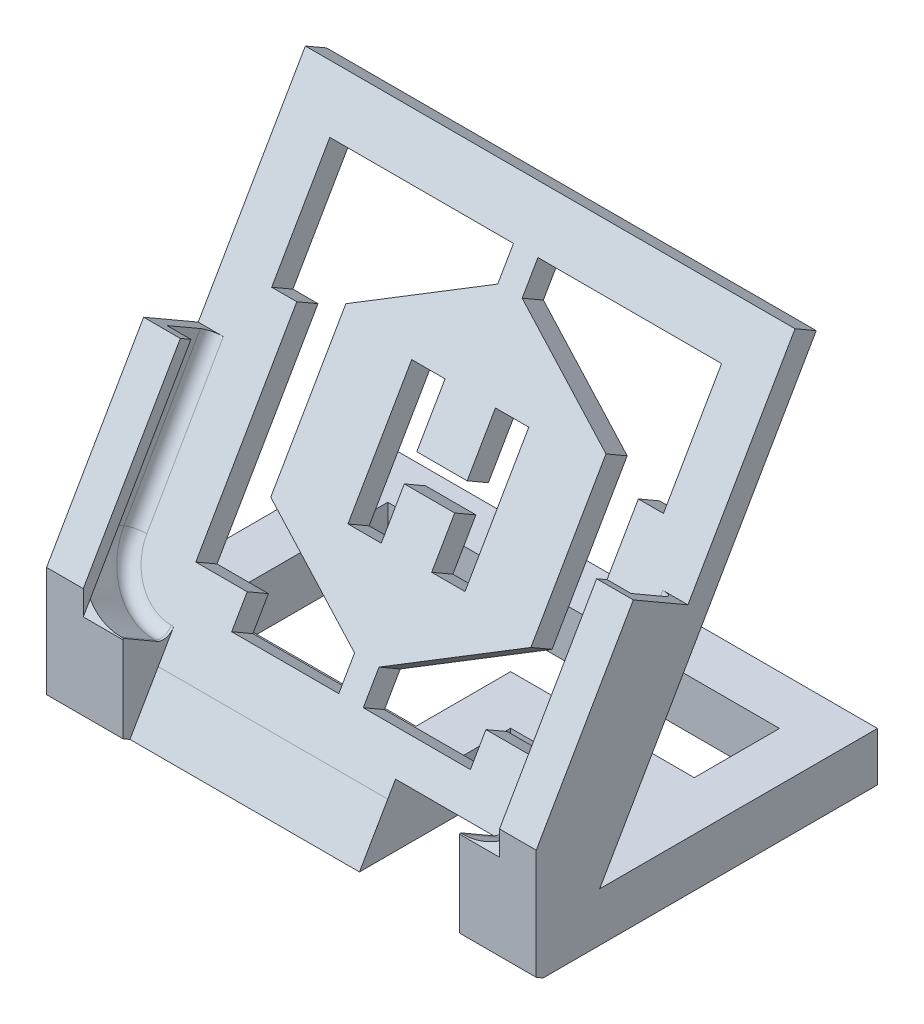
SolidWorks part; units mm, degrees
ref_plane "Front" through (0, 0, 0) normal (0, 0, 1) x (1, 0, 0)
ref_plane "Top" through (0, 0, 0) normal (0, 1, 0) x (1, 0, 0)
ref_plane "Right" through (0, 0, 0) normal (1, 0, 0) x (0, 0, -1)
sketch "Sketch1" plane through (0, 0, 0) normal (0, 1, 0) x (1, 0, 0)
  line L1 (-40, -25) -> (40, -25)
  line L2 (-40, -25) -> (-40, 25)
  line L3 (-40, 25) -> (40, 25)
  line L4 (40, -25) -> (40, 25)
  line L5 (-40, -25) -> (40, 25) construction
  line L6 (-40, 25) -> (40, -25) construction
  point P0 (0, 0)
  dimension "D1" = 80
  dimension "D2" = 50
extrude "Boss-Extrude1" add sketch "Sketch1" along normal blind 8
sketch "Sketch2" plane through (40, 0, 0) normal (1, 0, 0) x (0, 0, -1)
  line L0 (11.5359, 71.282) -> (-28.4641, 2)
  line L1 (11.5359, 71.282) -> (15, 69.282)
  line L2 (-28.4641, 2) -> (-25, 0)
  line L3 (15, 69.282) -> (-25, 0)
  line L4 (11.5359, 71.282) -> (-25, 0) construction
  line L5 (-28.4641, 2) -> (15, 69.282) construction
  line L6 (-25, 8) -> (-28.4641, 2)
  line L7 (-25, 0) -> (25, 0) construction
  line L8 (-25, 8) -> (25, 8) construction
  point P1 (-6.7321, 35.641)
  line M7 (25, 8) -> (-25, 8)
  dimension "D1" = 60
  dimension "D2" = 80
  dimension "D3" = 4
extrude "Boss-Extrude2" add sketch "Sketch2" against normal up to surface (80 mm away) contours L3 L1 L0 M7 up to face at (-40, 4, 0)
sketch "Sketch3" plane through (0, 12.8253, 22.2141) normal (0, 0.5, 0.866) x (1, 0, 0)
  line L0 (40, -2.5) -> (-40, -2.5)
  line L1 (40, 67.5) -> (40, -5.5718) construction
  line L2 (-40, -5.5718) -> (-40, 67.5) construction
  line L4 (-27.5, -2.5) -> (-27.5, -5.5718)
  line L5 (-40, -5.5718) -> (40, -5.5718) construction
  line L6 (0, -2.5) -> (0, -5.5718) construction
  line L7 (0, -5.5718) -> (-1.2175, -29.0774) construction
  line L8 (-37.9, -2.5) -> (-37.9, 32.5)
  line L9 (37.9, 32.5) -> (40, 32.5)
  line L10 (-37.9, 32.5) -> (-40, 32.5)
  line L11 (37.9, -2.5) -> (37.9, 32.5)
  line L12 (27.5, -2.5) -> (27.5, -5.5718)
  line L13 (-40, -12.5) -> (40, -12.5) construction
  line L14 (-40, -12.5) -> (40, -12.5)
  line M6 (-40, 67.5) -> (-40, -5.5718)
  line M7 (-40, -5.5718) -> (40, -5.5718)
  line M8 (40, -5.5718) -> (40, 67.5)
  dimension "D1" = 10
  dimension "D2" = 12.5
  dimension "D3" = 2.1
  dimension "D4" = 35
extrude "Boss-Extrude3" add sketch "Sketch3" along normal blind 8.3 contours L8 L10 L0 M6 | L4 L0 M6 M7 | L0 L12 M7 M8 | L11 L0 L9 M8
fillet "Fillet1" radius 10 2 edges at (-37.9, 12.7353, 27.0581) (37.9, 12.7353, 27.0581)
fillet "Fillet2" radius 2 6 edges at (27.7, 10.6603, 23.4641) (34.9711, 13.1968, 21.9996) (-27.7, 10.6603, 23.4641) (-34.9711, 13.1968, 21.9996) (37.9, 30.1458, 12.2141) (-37.9, 30.1458, 12.2141)
sketch "Sketch4" plane through (0, 0, 25) normal (0, 0, 1) x (1, 0, 0)
  line L4 (-40, 0) -> (40, 0)
  line L5 (40, 0) -> (40, 8)
  line L6 (27.5, 8) -> (-27.5, 8)
  line L7 (40, 0) -> (40, 8)
  line L8 (-40, 0) -> (40, 0)
  line L10 (27.5, 8) -> (-27.5, 8)
  line L14 (40, 8) -> (27.5, 8)
  line L15 (40, 8) -> (27.5, 8)
  line L16 (-27.5, 8) -> (-40, 8)
  line L17 (-27.5, 8) -> (-40, 8)
  line L18 (-40, 8) -> (-40, 0)
  line L19 (-40, 8) -> (-40, 0)
  dimension "D1" = 0
extrude "Boss-Extrude4" add sketch "Sketch4" along normal blind 10
chamfer "Chamfer2" distance 10 angle 60 1 edges at (0, 8, 35)
sketch "Sketch5" plane through (0, 12.8253, 22.2141) normal (0, 0.5, 0.866) x (1, 0, 0)
  line L0 (-27.5, -0.5) -> (-27.5, -5.5718) construction
  line L1 (-27.5, -0.5) -> (-27.5, -14.8094)
  line L2 (27.5, -0.5) -> (27.5, -5.5718) construction
  line L3 (27.5, -0.5) -> (27.5, -14.8094)
  line L6 (27.5, -5.5718) -> (-27.5, -5.5718)
  line L7 (-27.5, -5.5718) -> (-40, -5.5718)
  line L8 (-40, -5.5718) -> (-40, -14.8094)
  line L9 (-40, -14.8094) -> (40, -14.8094)
  line L10 (40, -14.8094) -> (40, -5.5718)
  line L11 (40, -5.5718) -> (27.5, -5.5718)
  line L12 (27.5, -5.5718) -> (-27.5, -5.5718)
  line L13 (-27.5, -5.5718) -> (-40, -5.5718)
  line L14 (-40, -5.5718) -> (-40, -14.8094)
  line L15 (-40, -14.8094) -> (40, -14.8094)
  line L16 (40, -14.8094) -> (40, -5.5718)
  line L17 (40, -5.5718) -> (27.5, -5.5718)
  line M8 (-27.5, -5.5718) -> (-40, -5.5718)
  line M9 (-40, -5.5718) -> (-40, -14.8094)
  line M10 (-40, -14.8094) -> (40, -14.8094)
  line M11 (40, -14.8094) -> (40, -5.5718)
  line M12 (40, -5.5718) -> (27.5, -5.5718)
  dimension "D1" = 0
extrude "Boss-Extrude5" add sketch "Sketch5" along normal up to surface (8.3 mm away) contours L1 M8 M9 M10 | L3 M12 M10 M11 up to face at (-34.3959, 23.6914, 25.5246)
sketch "Sketch6" plane through (0, 16.9753, 29.4021) normal (0, 0.5, 0.866) x (1, 0, 0)
  line L1 (-40, -14.8094) -> (-34, -14.8094)
  line L2 (-40, -14.8094) -> (-40, 32.5)
  line L3 (-40, 32.5) -> (-34, 32.5)
  line L4 (-34, -14.8094) -> (-34, 32.5)
  line L5 (40, -14.8094) -> (34, -14.8094)
  line L6 (-27.5, -2.5) -> (-27.9, -2.5)
  line L7 (-37.9, 7.5) -> (-37.9, 32.5)
  line L8 (-37.9, 32.5) -> (-40, 32.5)
  line L9 (-40, 32.5) -> (-40, -14.8094)
  line L10 (-40, -14.8094) -> (-27.5, -14.8094)
  line L11 (-27.5, -14.8094) -> (-27.5, -2.5)
  line L13 (-37.9, 7.5) -> (-37.9, 32.5)
  line L14 (-37.9, 32.5) -> (-40, 32.5)
  line L15 (-40, 32.5) -> (-40, -14.8094)
  line L16 (-40, -14.8094) -> (-34, -14.8094)
  line L18 (37.9, 32.5) -> (37.9, 7.5)
  line L19 (27.9, -2.5) -> (27.5, -2.5)
  line L20 (27.5, -2.5) -> (27.5, -14.8094)
  line L21 (27.5, -14.8094) -> (40, -14.8094)
  line L22 (40, -14.8094) -> (40, 32.5)
  line L23 (40, 32.5) -> (37.9, 32.5)
  line L24 (37.9, 32.5) -> (37.9, 7.5)
  line L25 (27.9, -2.5) -> (27.5, -2.5)
  line L27 (34, -14.8094) -> (40, -14.8094)
  line L28 (40, -14.8094) -> (40, 32.5)
  line L29 (40, 32.5) -> (37.9, 32.5)
  line L30 (40, -14.8094) -> (40, 32.5)
  line L31 (40, 32.5) -> (34, 32.5)
  line L32 (34, -14.8094) -> (34, 32.5)
  arc A1 (-37.9, 7.5) -> (-27.9, -2.5) centre (-27.9, 7.5) ccw
  arc A3 (27.9, -2.5) -> (37.9, 7.5) centre (27.9, 7.5) ccw
  arc A4 (27.9, -2.5) -> (37.9, 7.5) centre (27.9, 7.5) ccw
  dimension "D3" = 6
  dimension "D4" = 6
  dimension "D1" = 0
  dimension "D2" = 0
extrude "Boss-Extrude6" add sketch "Sketch6" along normal blind 2
chamfer "Chamfer3" distance 9 angle 60 6 edges at (30.75, 4.15, 36.8068) (-30.75, 4.15, 36.8068) (-34, 4.65, 37.6728) (-37, 5.15, 38.5389) (37, 5.15, 38.5389) (34, 4.65, 37.6728)
sketch "Sketch7" plane through (0, 12.8253, 22.2141) normal (0, 0.5, 0.866) x (1, 0, 0)
  line L0 (27.5, -3.0359) -> (27.5, -14.8094) construction
  line L1 (27.5, -0.5) -> (27.5, -5.5718) construction
  line L2 (27.5, -14.8094) -> (27.5, -8.9226) construction
  line L3 (27.5, -8.9226) -> (-25.3393, -8.9226) construction
  line L4 (27.5, -14.8094) -> (-27.5, -14.8094) construction
  line L5 (27.5, -3.0359) -> (10, -3.0359)
  line L6 (27.5, -3.0359) -> (27.5, -14.8094)
  line L7 (27.5, -14.8094) -> (10, -14.8094)
  line L8 (10, -3.0359) -> (10, -14.8094)
  dimension "D1" = 17.5
extrude "Cut-Extrude1" cut sketch "Sketch7" against normal blind 12
sketch "Sketch8" plane through (0, 8, 0) normal (0, 1, 0) x (1, 0, 0)
  line L0 (10, -20.3812) -> (10, -19.9282) construction
  line L1 (27.5, -19.9282) -> (10, -19.9282)
  line L2 (27.5, -19.9282) -> (27.5, -4.9282)
  line L3 (27.5, -4.9282) -> (10, -4.9282)
  line L4 (10, -19.9282) -> (10, -4.9282)
  dimension "D1" = 15
extrude "Cut-Extrude2" cut sketch "Sketch8" against normal blind 12
sketch "Sketch9" plane through (0, 8, 0) normal (0, 1, 0) x (1, 0, 0)
  line L0 (2, 3.0718) -> (32, 3.0718)
  line L1 (32, 3.0718) -> (32, 3.0718)
  line L2 (32, 3.0718) -> (32, 3.0718)
  line L3 (32, 3.0718) -> (32, 17)
  line L4 (32, 17) -> (-32, 17)
  line L5 (-32, 17) -> (-32, -12.3812)
  line L6 (-32, -12.3812) -> (2, -12.3812)
  line L7 (2, -12.3812) -> (2, 3.0718)
  line L8 (10, -4.9282) -> (27.5, -4.9282)
  line L9 (27.5, -4.9282) -> (27.5, -20.3812)
  line L10 (27.5, -20.3812) -> (40, -20.3812)
  line L11 (40, -20.3812) -> (40, 25)
  line L12 (40, 25) -> (-40, 25)
  line L13 (-40, 25) -> (-40, -20.3812)
  line L14 (-40, -20.3812) -> (10, -20.3812)
  line L15 (10, -20.3812) -> (10, -4.9282)
  line L16 (10, -4.9282) -> (27.5, -4.9282)
  line L17 (27.5, -4.9282) -> (27.5, -20.3812)
  line L18 (27.5, -20.3812) -> (40, -20.3812)
  line L19 (40, -20.3812) -> (40, 25)
  line L20 (40, 25) -> (-40, 25)
  line L21 (-40, 25) -> (-40, -20.3812)
  line L22 (-40, -20.3812) -> (10, -20.3812)
  line L23 (10, -20.3812) -> (10, -4.9282)
  dimension "D1" = 0
  dimension "D2" = 8
extrude "Cut-Extrude3" cut sketch "Sketch9" against normal blind 12 contours L6 L7 L0 L3 L4 L5
sketch "Sketch10" plane through (0, 12.8253, 22.2141) normal (0, 0.5, 0.866) x (1, 0, 0)
  line L0 (2, 2.4282) -> (2, 4.9641)
  line L1 (2, 4.9641) -> (19.5, 4.9641)
  line L2 (19.5, 4.9641) -> (19.5, 7.5)
  line L3 (19.5, 7.5) -> (27.9, 7.5)
  line L4 (27.9, 7.5) -> (27.9, 40.5)
  line L5 (27.9, 40.5) -> (32, 40.5)
  line L6 (32, 40.5) -> (32, 59.5)
  line L7 (32, 59.5) -> (-32, 59.5)
  line L8 (-32, 59.5) -> (-32, 40.5)
  line L9 (-32, 40.5) -> (-27.9, 40.5)
  line L10 (-27.9, 40.5) -> (-27.9, 7.5)
  line L11 (-27.9, 7.5) -> (-19.5, 7.5)
  line L12 (-19.5, 7.5) -> (-19.5, 2.4282)
  line L13 (-19.5, 2.4282) -> (2, 2.4282)
  line L14 (10, -5.5718) -> (10, -3.0359)
  line L15 (10, -3.0359) -> (27.5, -3.0359)
  line L16 (27.5, -3.0359) -> (27.5, -0.5)
  line L17 (27.5, -0.5) -> (27.9, -0.5)
  line L18 (35.9, 7.5) -> (35.9, 32.5)
  line L19 (35.9, 32.5) -> (40, 32.5)
  line L20 (40, 32.5) -> (40, 67.5)
  line L21 (40, 67.5) -> (-40, 67.5)
  line L22 (-40, 67.5) -> (-40, 32.5)
  line L23 (-40, 32.5) -> (-35.9, 32.5)
  line L24 (-35.9, 32.5) -> (-35.9, 7.5)
  line L25 (-27.9, -0.5) -> (-27.5, -0.5)
  line L26 (-27.5, -0.5) -> (-27.5, -5.5718)
  line L27 (-27.5, -5.5718) -> (10, -5.5718)
  line L28 (10, -5.5718) -> (10, -3.0359)
  line L29 (10, -3.0359) -> (27.5, -3.0359)
  line L30 (27.5, -3.0359) -> (27.5, -0.5)
  line L31 (27.5, -0.5) -> (27.9, -0.5)
  line L32 (35.9, 7.5) -> (35.9, 32.5)
  line L33 (35.9, 32.5) -> (40, 32.5)
  line L34 (40, 32.5) -> (40, 67.5)
  line L35 (40, 67.5) -> (-40, 67.5)
  line L36 (-40, 67.5) -> (-40, 32.5)
  line L37 (-40, 32.5) -> (-35.9, 32.5)
  line L38 (-35.9, 32.5) -> (-35.9, 7.5)
  line L39 (-27.9, -0.5) -> (-27.5, -0.5)
  line L40 (-27.5, -0.5) -> (-27.5, -5.5718)
  line L41 (-27.5, -5.5718) -> (10, -5.5718)
  arc A0 (27.9, 7.5) -> (27.9, 7.5) centre (27.9, 7.5) ccw
  arc A1 (-27.9, 7.5) -> (-27.9, 7.5) centre (-27.9, 7.5) ccw
  arc A2 (27.9, -0.5) -> (35.9, 7.5) centre (27.9, 7.5) ccw
  arc A3 (-35.9, 7.5) -> (-27.9, -0.5) centre (-27.9, 7.5) ccw
  arc A4 (27.9, -0.5) -> (35.9, 7.5) centre (27.9, 7.5) ccw
  arc A5 (-35.9, 7.5) -> (-27.9, -0.5) centre (-27.9, 7.5) ccw
  dimension "D1" = 0
  dimension "D2" = 8
extrude "Cut-Extrude4" cut sketch "Sketch10" against normal up to surface (4 mm away) contours L12 L13 L0 L1 L2 L3 L4 L5 L6 L7 L8 L9 L10 L11 up to face at (9.375, 23.3695, 11.5076)
sketch "Sketch11" plane through (0, 12.8253, 22.2141) normal (0, 0.5, 0.866) x (1, 0, 0)
  line L0 (0, 59.5) -> (0, 2.4282) construction
  line L1 (32, 59.5) -> (-32, 59.5) construction
  line L2 (-19.5, 2.4282) -> (2, 2.4282) construction
  line L3 (-9.5637, 30.9641) -> (9.5637, 30.9641) construction
  line L4 (0, 55.5) -> (-21.2487, 43.2321)
  line L5 (-21.2487, 43.2321) -> (-21.2487, 18.6962)
  line L6 (-21.2487, 18.6962) -> (0, 6.4282)
  line L7 (0, 6.4282) -> (21.2487, 18.6962)
  line L8 (21.2487, 18.6962) -> (21.2487, 43.2321)
  line L9 (21.2487, 43.2321) -> (0, 55.5)
  line L16 (-9.5637, 41.3837) -> (-4.1156, 41.3837)
  line L17 (-9.5637, 41.3837) -> (-9.5637, 20.5445)
  line L18 (-9.5637, 20.5445) -> (-4.1156, 20.5445)
  line L19 (-4.1156, 41.3837) -> (-4.1156, 20.5445)
  line L20 (-4.1156, 32.14) -> (4.1156, 32.14)
  line L21 (-4.1156, 32.14) -> (-4.1156, 28.0668)
  line L22 (-4.1156, 28.0668) -> (4.1156, 28.0668)
  line L23 (0, 32.14) -> (0, 28.0668)
  line L24 (-4.1156, 32.14) -> (-4.1156, 28.0668) construction
  line L25 (4.1156, 32.14) -> (4.1156, 28.0668) construction
  line L26 (4.1156, 32.14) -> (4.1156, 28.0668)
  line L27 (4.1156, 41.3837) -> (4.1156, 20.5445)
  line L28 (9.5637, 20.5445) -> (4.1156, 20.5445)
  line L29 (9.5637, 41.3837) -> (9.5637, 20.5445)
  line L30 (9.5637, 41.3837) -> (4.1156, 41.3837)
  line L32 (-1.5941, 32.14) -> (-1.5941, 28.0668) construction
  line L33 (72.4505, 296.1575) -> (461.1172, 296.1575) construction
  line L34 (-2, 59.5) -> (2, 59.5)
  line L35 (-2, 59.5) -> (-2, 2.4282)
  line L36 (-2, 2.4282) -> (2, 2.4282)
  line L37 (2, 59.5) -> (2, 2.4282)
  circle A0 centre (0, 30.9641) radius 21.2487 construction
  point P18 (9.6422, 41.3837)
  point P19 (4.3666, 33.3311)
  point P20 (0, 0)
  point P21 (-9.1547, 30.9641)
  point P31 (-4.1156, 30.9641)
  point P40 (4.1156, 30.9641)
  point P43 (0, 0)
  line M29 (-32, 59.5) -> (32, 59.5)
  line M36 (2, 4.9641) -> (2, 2.4282)
  line M37 (2, 2.4282) -> (-19.5, 2.4282)
  dimension "D2" = 4
extrude "Boss-Extrude7" add sketch "Sketch11" against normal up to surface (4 mm away) contours L35 L4 L5 L6 L22 L19 L18 L17 L16 L20 | L9 L37 L20 L27 L30 L29 L28 L22 L7 L8 | L37 L9 L4 L35 L20 | L37 L35 L4 L9 M29 | L37 L7 L6 L35 M37 M36 | L37 L22 L35 L6 L7 up to face at (0.2857, 30.978, 7.1148)
sketch "Sketch12" plane through (0, 12.8253, 22.2141) normal (0, 0.5, 0.866) x (1, 0, 0)
  line L12 (-4.1156, 32.14) -> (-4.1156, 41.3837)
  line L13 (-2, 54.3453) -> (-2, 59.5)
  line L14 (-2, 54.3453) -> (-2, 59.5)
  line L15 (-21.2487, 43.2321) -> (-2, 54.3453)
  line L16 (-21.2487, 43.2321) -> (-2, 54.3453)
  line L17 (-21.2487, 18.6962) -> (-21.2487, 43.2321)
  line L18 (-21.2487, 18.6962) -> (-21.2487, 43.2321)
  line L19 (-2, 7.5829) -> (-21.2487, 18.6962)
  line L20 (-2, 7.5829) -> (-21.2487, 18.6962)
  line L21 (-9.5637, 20.5445) -> (-4.1156, 20.5445)
  line L22 (-9.5637, 41.3837) -> (-9.5637, 20.5445)
  line L23 (-4.1156, 41.3837) -> (-9.5637, 41.3837)
  line L24 (-4.1156, 32.14) -> (-4.1156, 41.3837)
  line L33 (-9.5637, 20.5445) -> (-4.1156, 20.5445)
  line L34 (-9.5637, 41.3837) -> (-9.5637, 20.5445)
  line L35 (-4.1156, 41.3837) -> (-9.5637, 41.3837)
  line L36 (-2, 59.5) -> (-32, 59.5)
  line L37 (-2, 2.4282) -> (-2, 7.5829)
  line L38 (-2, 2.4282) -> (-2, 7.5829)
  line L39 (-19.5, 2.4282) -> (-2, 2.4282)
  line L40 (-19.5, 2.4282) -> (19.5, 2.4282)
  line L41 (-19.5, 7.5) -> (-19.5, 2.4282)
  line L42 (-19.5, 7.5) -> (-19.5, 2.4282)
  line L43 (-27.9, 7.5) -> (-19.5, 7.5)
  line L44 (-27.9, 7.5) -> (-19.5, 7.5)
  line L45 (-27.9, 40.5) -> (-27.9, 7.5)
  line L46 (-27.9, 40.5) -> (-27.9, 7.5)
  line L47 (-32, 40.5) -> (-27.9, 40.5)
  line L48 (-2, 59.5) -> (-32, 59.5)
  line L60 (2, 59.5) -> (2, 54.3453)
  line L61 (32, 59.5) -> (2, 59.5)
  line L62 (32, 40.5) -> (32, 59.5)
  line L63 (27.9, 40.5) -> (32, 40.5)
  line L64 (27.9, 7.5) -> (27.9, 40.5)
  line L65 (19.5, 7.5) -> (27.9, 7.5)
  line L66 (19.5, 4.9641) -> (19.5, 7.5)
  line L67 (2, 4.9641) -> (19.5, 4.9641)
  line L68 (2, 7.5829) -> (2, 4.9641)
  line L69 (21.2487, 18.6962) -> (2, 7.5829)
  line L70 (21.2487, 43.2321) -> (21.2487, 18.6962)
  line L71 (2, 54.3453) -> (21.2487, 43.2321)
  line L72 (2, 59.5) -> (2, 54.3453)
  line L73 (32, 59.5) -> (2, 59.5)
  line L74 (32, 40.5) -> (32, 59.5)
  line L75 (27.9, 40.5) -> (32, 40.5)
  line L76 (27.9, 2.4282) -> (27.9, 40.5)
  line L77 (19.5, 7.5) -> (27.9, 7.5)
  line L78 (19.5, 2.4282) -> (19.5, 7.5)
  line L79 (2, 4.9641) -> (19.5, 4.9641)
  line L80 (2, 7.5829) -> (2, -5.5718)
  line L81 (21.2487, 18.6962) -> (2, 7.5829)
  line L82 (21.2487, 43.2321) -> (21.2487, 18.6962)
  line L83 (2, 54.3453) -> (21.2487, 43.2321)
  line L84 (-32, 40.5) -> (-27.9, 40.5)
  line L85 (-32, 59.5) -> (-32, 40.5)
  line L86 (10, -5.5718) -> (10, -3.0359)
  line L87 (10, -3.0359) -> (27.5, -3.0359)
  line L88 (27.5, -3.0359) -> (27.5, -0.5)
  line L89 (27.5, -0.5) -> (27.9, -0.5)
  line L90 (35.9, 7.5) -> (35.9, 32.5)
  line L91 (35.9, 32.5) -> (40, 32.5)
  line L92 (40, 32.5) -> (40, 67.5)
  line L93 (40, 67.5) -> (-40, 67.5)
  line L94 (-40, 67.5) -> (-40, 32.5)
  line L95 (-40, 32.5) -> (-35.9, 32.5)
  line L96 (-35.9, 32.5) -> (-35.9, 7.5)
  line L97 (-27.9, -0.5) -> (-27.5, -0.5)
  line L98 (-27.5, -0.5) -> (-27.5, -5.5718)
  line L99 (-27.5, -5.5718) -> (10, -5.5718)
  line L100 (10, -5.5718) -> (10, -3.0359)
  line L101 (10, -3.0359) -> (27.5, -3.0359)
  line L102 (27.5, -3.0359) -> (27.5, -0.5)
  line L103 (27.5, -0.5) -> (27.9, -0.5)
  line L104 (35.9, 7.5) -> (35.9, 32.5)
  line L105 (35.9, 32.5) -> (40, 32.5)
  line L106 (40, 32.5) -> (40, 67.5)
  line L107 (40, 67.5) -> (-40, 67.5)
  line L108 (-40, 67.5) -> (-40, 32.5)
  line L109 (-40, 32.5) -> (-35.9, 32.5)
  line L110 (-35.9, 32.5) -> (-35.9, 7.5)
  line L111 (-27.9, -0.5) -> (-27.5, -0.5)
  line L112 (-27.5, -0.5) -> (-27.5, -5.5718)
  line L114 (-32, 59.5) -> (-32, 40.5)
  line L115 (4.1156, 32.14) -> (-4.1156, 32.14)
  line L116 (4.1156, 32.14) -> (-4.1156, 32.14)
  line L118 (4.1156, 41.3837) -> (4.1156, 32.14)
  line L119 (4.1156, 41.3837) -> (4.1156, 32.14)
  line L120 (9.5637, 41.3837) -> (4.1156, 41.3837)
  line L121 (9.5637, 41.3837) -> (4.1156, 41.3837)
  line L122 (9.5637, 20.5445) -> (9.5637, 41.3837)
  line L123 (9.5637, 20.5445) -> (9.5637, 41.3837)
  line L124 (4.1156, 20.5445) -> (9.5637, 20.5445)
  line L125 (4.1156, 20.5445) -> (9.5637, 20.5445)
  line L126 (4.1156, 28.0668) -> (4.1156, 20.5445)
  line L127 (4.1156, 28.0668) -> (4.1156, 20.5445)
  line L128 (-4.1156, 28.0668) -> (4.1156, 28.0668)
  line L129 (-4.1156, 28.0668) -> (4.1156, 28.0668)
  line L130 (-4.1156, 20.5445) -> (-4.1156, 28.0668)
  line L131 (-4.1156, 20.5445) -> (-4.1156, 28.0668)
  line L134 (-27.5, -5.5718) -> (10, -5.5718)
  arc A2 (27.9, -0.5) -> (35.9, 7.5) centre (27.9, 7.5) ccw
  arc A3 (-35.9, 7.5) -> (-27.9, -0.5) centre (-27.9, 7.5) ccw
  arc A4 (27.9, -0.5) -> (35.9, 7.5) centre (27.9, 7.5) ccw
  arc A5 (-35.9, 7.5) -> (-27.9, -0.5) centre (-27.9, 7.5) ccw
  dimension "D1" = 0
  dimension "D2" = 0
  dimension "D3" = 0
  dimension "D4" = 0
extrude "Cut-Extrude5" cut sketch "Sketch12" against normal up to next contours L79 L80 L40 L78
